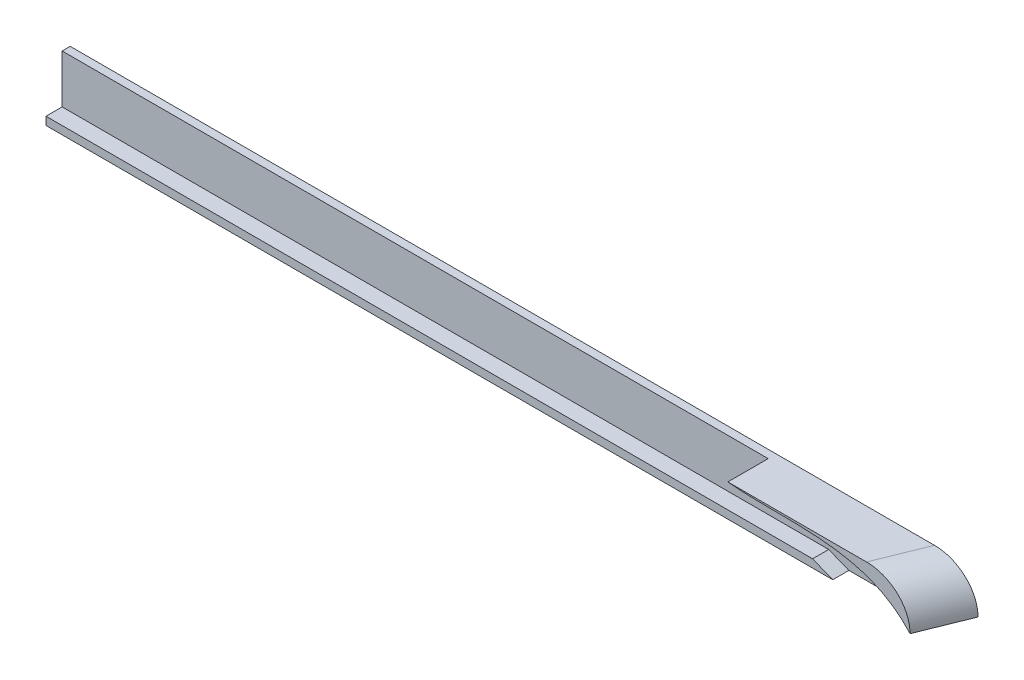
SolidWorks part; units mm, degrees
ref_plane "Płaszczyzna przednia" through (0, 0, 0) normal (0, 0, 1) x (1, 0, 0)
ref_plane "Płaszczyzna górna" through (0, 0, 0) normal (0, 1, 0) x (1, 0, 0)
ref_plane "Płaszczyzna prawa" through (0, 0, 0) normal (1, 0, 0) x (0, 0, -1)
sketch "Sketch1" plane through (0, 0, 0) normal (0, 0, 1) x (1, 0, 0)
  line L1 (-186.05, 8.825) -> (28.95, 8.825)
  line L2 (-186.05, 8.825) -> (-186.05, -5.175)
  line L3 (-186.05, -5.175) -> (28.95, -5.175)
  line L4 (28.95, 8.825) -> (28.95, -5.175)
  dimension "D1" = 14
  dimension "D2" = 215
extrude "Boss-Extrude1" add sketch "Sketch1" along normal blind 2
sketch "Sketch2" plane through (0, 0, 2) normal (0, 0, 1) x (1, 0, 0)
  line L0 (28.95, -5.175) -> (28.95, 8.825) construction
  line L1 (-186.05, -5.175) -> (28.95, -5.175)
  line L2 (-186.05, -5.175) -> (-186.05, -3.175)
  line L3 (-186.05, -3.175) -> (28.95, -3.175)
  line L4 (28.95, -5.175) -> (28.95, -3.175)
  dimension "D1" = 2
extrude "Boss-Extrude2" add sketch "Sketch2" along normal blind 4
sketch "Sketch3" plane through (0, 0, 0) normal (0, 0, -1) x (-1, 0, 0)
  line L0 (-28.95, 8.825) -> (-28.95, -1.175)
  line L1 (-28.95, -5.175) -> (-28.95, 8.825) construction
  line L2 (-28.95, -1.175) -> (-38.95, -1.175)
  line L3 (-28.95, 8.825) -> (-38.95, 8.825)
  line L4 (-38.95, 8.825) -> (-38.95, -1.175)
  dimension "D1" = 10
  dimension "D2" = 10
extrude "Boss-Extrude3" add sketch "Sketch3" against normal blind 2
sketch "Sketch4" plane through (0, 0, 6) normal (0, 0, 1) x (1, 0, 0)
  line L0 (28.95, -5.175) -> (8.95, -5.175)
  line L1 (-186.05, -5.175) -> (28.95, -5.175) construction
  line L2 (8.95, -5.175) -> (3.95, -3.175)
  line L3 (28.95, -3.175) -> (-186.05, -3.175) construction
  line L4 (3.95, -3.175) -> (28.95, -3.175)
  line L5 (28.95, -3.175) -> (28.95, -5.175)
  dimension "D1" = 20
  dimension "D2" = 25
extrude "Cut-Extrude1" cut sketch "Sketch4" against normal blind 4
sketch "Sketch8" plane through (-186.05, 0, 0) normal (-1, 0, 0) x (0, 0, 1)
  line L0 (2, 8.825) -> (12, 8.825)
  line L1 (12, 8.825) -> (12, -1.175)
  line L2 (12, -1.175) -> (2, -1.175)
  line L3 (2, 8.825) -> (2, -3.175) construction
  line L4 (2, -1.175) -> (2, 8.825)
  dimension "D1" = 10
  dimension "D2" = 10
extrude "Boss-Extrude4" add sketch "Sketch8" against normal blind 50 from offset 175 offset against normal yes
sketch "Sketch12" plane through (0, -1.175, 0) normal (0, -1, 0) x (1, 0, 0)
  line L0 (38.95, 0) -> (34.1017, 12)
  line L1 (38.95, 12) -> (-11.05, 12) construction
  line L2 (34.1017, 12) -> (38.95, 12)
  line L3 (38.95, 12) -> (38.95, 0)
  line L4 (38.95, 0) -> (28.95, 0) construction
  dimension "D1" = 68
extrude "Cut-Extrude5" cut sketch "Sketch12" against normal blind 50
fillet "Fillet2" radius 10 1 edges at (36.5258, 8.825, 6)
sketch "Sketch13" plane through (0, 0, 12) normal (0, 0, 1) x (1, 0, 0)
  line L0 (23.3163, 8.825) -> (-11.05, 8.825) construction
  line L1 (-11.05, -1.175) -> (-11.05, 8.825) construction
  line L2 (-11.05, 8.825) -> (-11.05, -1.175) construction
  line L3 (-11.05, 8.825) -> (-11.05, -1.175)
  line L4 (-11.05, -1.175) -> (34.1017, -1.175)
  spline S0 degree 3 poles (-11.05, 8.825) (3.6062, 7.3343) (22.994, 11.3349) (34.1017, -1.175) knots 0 0 0 0 1 1 1 1
  dimension "D1" = 0.5
  dimension "D2" = 4.5
  dimension "D3" = 17
  dimension "D4" = 38
extrude "Cut-Extrude6" cut sketch "Sketch13" against normal blind 10
